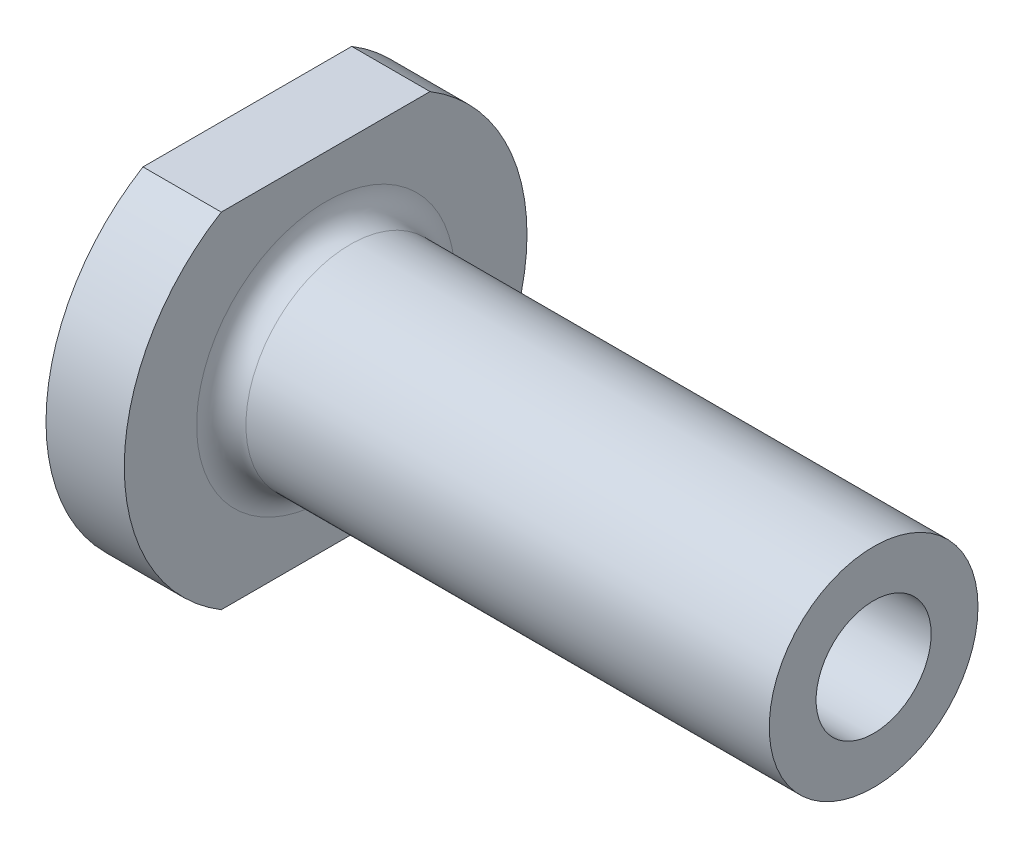
SolidWorks part; units mm, degrees
material "Ti-6Al-4VSolution treated and aged (SS)"
ref_plane "Front Plane" through (0, 0, 0) normal (0, 0, 1) x (1, 0, 0)
ref_plane "Top Plane" through (0, 0, 0) normal (0, 1, 0) x (1, 0, 0)
ref_plane "Right Plane" through (0, 0, 0) normal (1, 0, 0) x (0, 0, -1)
sketch "Sketch1" plane through (0, 0, 0) normal (0, 0, 1) x (1, 0, 0)
  line L0 (0, 0) -> (-17.6508, 0) construction
  line L1 (0, 0) -> (38.1, 0)
  line L2 (38.1, 0) -> (38.1, 6.35)
  line L3 (38.1, 6.35) -> (4.7625, 6.35)
  line L4 (4.7625, 6.35) -> (4.7625, 12.25)
  line L5 (4.7625, 12.25) -> (0, 12.25)
  line L6 (0, 12.25) -> (0, 0)
  dimension "D1" = 12.7
  dimension "D2" = 38.1
  dimension "D3" = 4.7625
  dimension "D4" = 24.5
revolve "Revolve1" add sketch "Sketch1" angle 360 about L0
fillet "Fillet1" radius 1.5 1 edges at (4.7625, 0, -6.35)
hole_wizard "5/16-18 MAKE SURE TO CHANGE THIS" positions "Sketch2" profile "Sketch3" tap size "M8x1.0" standard "ANSI Metric" end condition through all
sketch "Sketch2" plane through (38.1, 0, 0) normal (1, 0, 0) x (0, 0, -1)
  point P0 (0, 0)
sketch "Sketch3" plane through (38.1, 0, 0) normal (0, 1, 0) x (0, 0, -1)
  line L0 (0, 0) -> (0, 38.1)
  line L1 (0, 38.1) -> (3.5, 38.1)
  line L2 (3.5, 38.1) -> (3.5, 0)
  line L5 (3.5, 0) -> (0, 0)
  line L11 (0, -6.35) -> (0, 107.95) construction
  dimension "Thru Tap Drill Dia." = 7
  dimension "Thru Tap Drill Depth" = 38.1
cosmetic thread "Hole Thread1" parameters "D2"=8
sketch "Sketch4" plane through (0, 0, 0) normal (-1, 0, 0) x (0, 0, 1)
  line L0 (-6.35, 10.4757) -> (6.35, 10.4757)
  line L5 (6.35, -10.4757) -> (-6.35, -10.4757)
  arc A1 (6.35, 10.4757) -> (-6.35, 10.4757) centre (0, 0) ccw
  circle A2 centre (0, 0) radius 12.25
  arc A3 (-6.35, -10.4757) -> (6.35, -10.4757) centre (0, 0) ccw
  dimension "D1" = 0
  dimension "D2" = 12.7
extrude "Cut-Extrude1" cut sketch "Sketch4" against normal through all
equation "\"D4@Sketch1\"=24.5mm"
